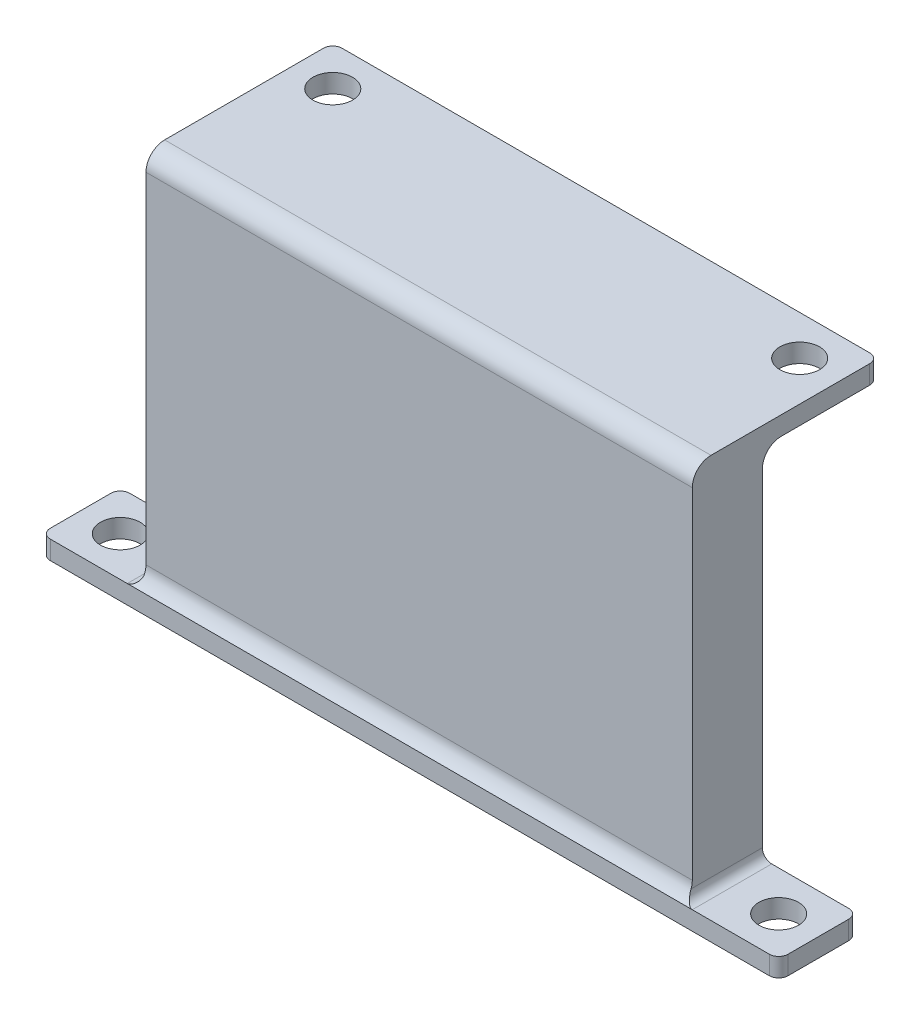
SolidWorks part; units mm, degrees
ref_plane "Front Plane" through (0, 0, 0) normal (0, 0, 1) x (1, 0, 0)
ref_plane "Top Plane" through (0, 0, 0) normal (0, 1, 0) x (1, 0, 0)
ref_plane "Right Plane" through (0, 0, 0) normal (1, 0, 0) x (0, 0, -1)
sketch "Sketch1" plane through (0, 0, 0) normal (0, 1, 0) x (1, 0, 0)
  line L0 (-79, 4.25) -> (0, 4.25) construction
  line L1 (0, 0) -> (-79, 0)
  line L2 (0, 0) -> (0, 8.5)
  line L3 (0, 8.5) -> (-79, 8.5)
  line L4 (-79, 0) -> (-79, 8.5)
  circle A0 centre (-74.75, 4.25) radius 2.125
  circle A1 centre (-4.25, 4.25) radius 2.125
  dimension "D1" = 4.25
  dimension "D4" = 70.5
  dimension "D2" = 4.25
  dimension "D3" = 4.25
  dimension "D5" = 4.25
extrude "Boss-Extrude1" add sketch "Sketch1" along normal blind 2
sketch "Sketch3" plane through (0, 2, 0) normal (0, 1, 0) x (1, 0, 0)
  line L0 (-39.5, 8.5) -> (-39.5, 0) construction
  line L1 (0, 8.5) -> (-79, 8.5) construction
  line L2 (-79, 0) -> (0, 0) construction
  line L4 (-68.75, 1) -> (-10.25, 1)
  line L5 (-68.75, 1) -> (-68.75, 8.5)
  line L6 (-68.75, 8.5) -> (-10.25, 8.5)
  line L7 (-10.25, 1) -> (-10.25, 8.5)
  line L8 (-68.75, 1) -> (-10.25, 8.5) construction
  line L9 (-68.75, 8.5) -> (-10.25, 1) construction
  point P4 (-39.5, 4.75)
  dimension "D1" = 7.5
  dimension "D2" = 58.5
extrude "Boss-Extrude2" add sketch "Sketch3" along normal blind 40.14
sketch "Sketch4" plane through (0, 0, -8.5) normal (0, 0, -1) x (-1, 0, 0)
  line L0 (68.75, 42.14) -> (68.75, 2) construction
  line L1 (10.25, 42.14) -> (68.75, 42.14)
  line L2 (10.25, 42.14) -> (10.25, 40.14)
  line L3 (10.25, 40.14) -> (68.75, 40.14)
  line L4 (68.75, 42.14) -> (68.75, 40.14)
  dimension "D1" = 2
extrude "Boss-Extrude3" add sketch "Sketch4" along normal blind 12.5
sketch "Sketch5" plane through (0, 42.14, 0) normal (0, 1, 0) x (1, 0, 0)
  line L0 (-10.25, 16.75) -> (-68.75, 16.75) construction
  line L1 (-10.25, 1) -> (-10.25, 21) construction
  line L2 (-68.75, 21) -> (-68.75, 1) construction
  line L3 (-68.75, 21) -> (-10.25, 21) construction
  circle A0 centre (-14.5, 16.75) radius 2.125
  circle A1 centre (-64.5, 16.75) radius 2.125
  dimension "D2" = 4.25
  dimension "D1" = 4.25
  dimension "D3" = 4.25
  dimension "D4" = 4.25
extrude "Cut-Extrude1" cut sketch "Sketch5" against normal up to next
fillet "Fillet1" radius 2 2 edges at (-39.5, 2, -1)
fillet "Fillet2" radius 1 6 edges at (-79, 1, 0) (-79, 1, -8.5) (-68.75, 41.14, -21) (-10.25, 41.14, -21) (0, 1, -8.5) (0, 1, 0)
fillet "Fillet3" radius 2 1 edges at (-39.5, 42.14, -1)
fillet "Fillet4" radius 1 1 edges
fillet "Fillet5" radius 1 1 edges
